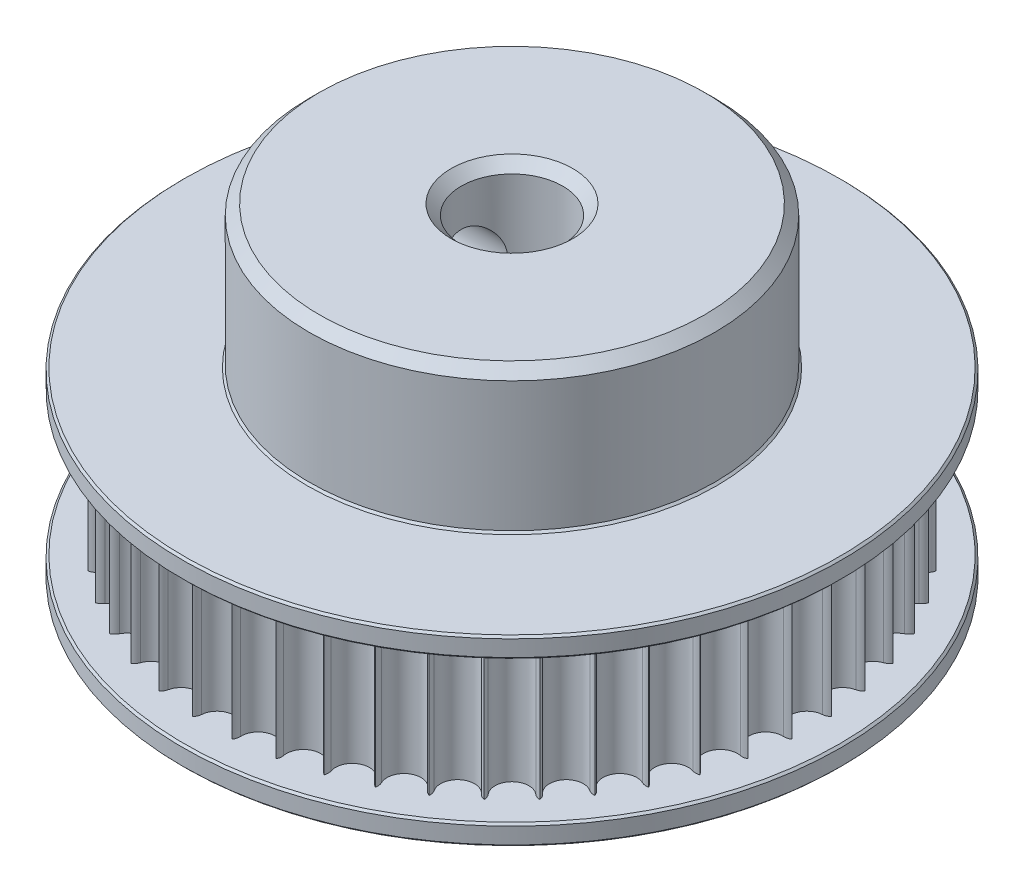
SolidWorks part; units mm, degrees
ref_plane "Front plan" through (0, 0, 0) normal (0, 0, 1) x (1, 0, 0)
ref_plane "Top plan" through (0, 0, 0) normal (0, 1, 0) x (1, 0, 0)
ref_plane "Right plan" through (0, 0, 0) normal (1, 0, 0) x (0, 0, -1)
sketch "Skica2" plane through (0, 0, 0) normal (0, 0, 1) x (1, 0, 0)
  line L0 (10, 8.5) -> (2.5, 8.5)
  line L1 (2.5, 8.5) -> (2.5, -8.5)
  line L2 (2.5, -8.5) -> (3.5, -8.5)
  line L3 (0, -8.5) -> (0, 8.5) construction
  line L4 (0, 8.5) -> (2.5, 8.5)
  line L5 (0, -8.5) -> (2.5, -8.5)
  line L6 (3.5, -8.5) -> (3.5, -7.5)
  line L7 (16.25, 0.5) -> (15, 0.5)
  line L8 (15, 0.5) -> (15, -6.5)
  line L9 (16.25, 0.5) -> (16.25, 1.5)
  line L12 (16.25, -7.5) -> (3.5, -7.5)
  line L13 (16.25, 1.5) -> (10, 1.5)
  line L14 (16.25, -7.5) -> (16.25, -6.5)
  line L15 (15, -6.5) -> (16.25, -6.5)
  line L16 (10, 1.5) -> (10, 8.5)
  point P2 (6.9432, -7.5)
  point P6 (9.875, -7.5)
  point P7 (0, 0)
  point P17 (7.5179, -7.5)
  dimension "D2" = 1
  dimension "D6" = 32.5
  dimension "D3" = 30
  dimension "D1" = 5
  dimension "D8" = 17
  dimension "D4" = 1
  dimension "D7" = 20
  dimension "D9" = 7
  dimension "D5" = 1
revolve "Revolute" add sketch "Skica2" angle 360 about L3 region at (8.0389, -0.5371, 0)
sketch "Sketch2" plane through (0, 0.5, 0) normal (0, -1, 0) x (1, 0, 0)
  line L0 (0, 0) -> (0, 14.5385) construction
  line L1 (0, 0) -> (5.0579, 14.1215) construction
  line L3 (0, 0) -> (-2.1506, 14.845) construction
  circle A1 centre (0, 0) radius 13.7025 construction
  circle A2 centre (0, 0) radius 14.5 construction
  arc A3 (-0.8336, 14.476) -> (0.8336, 14.476) centre (0, 14.5385) ccw
  arc A7 (-1.3782, 14.9366) -> (-2.1506, 14.845) centre (0, 0) ccw
  arc A8 (0, 16.4495) -> (2.1506, 14.845) centre (0.5839, 14.9886) cw
  circle A9 centre (0, 0) radius 15 construction
  arc A10 (1.3782, 14.9366) -> (2.1506, 14.845) centre (0, 0) cw
  arc A11 (1.3782, 14.9366) -> (0.8336, 14.476) centre (1.3322, 14.4387) ccw
  arc A12 (0, 16.4495) -> (-2.1506, 14.845) centre (-0.5839, 14.9886) ccw
  arc A13 (-1.3782, 14.9366) -> (-0.8336, 14.476) centre (-1.3322, 14.4387) cw
  point P0 (0.8326, 11.926)
  dimension "D2" = 1
  dimension "D4" = 0.836
  dimension "D6" = 30
  dimension "D3" = 1.5733
extrude "Cut-Extrude3" cut sketch "Sketch2" along normal up to surface (7 mm away) up to face at (16.25, -6.5, 0)
pattern_circular "CirPattern1" count 48 over 360 about axis through (0, -8.5, 0) along (0, -1, 0) of "Cut-Extrude3"
sketch "Sketch3" plane through (0, 0, 0) normal (1, 0, 0) x (0, 0, -1)
  line L0 (0, 8.5) -> (0, 0.5) construction
  line L1 (2.5, 8.5) -> (-2.5, 8.5) construction
  circle A0 centre (0, 4.5) radius 1.65
  dimension "D1" = 3.3
extrude "Cut-Extrude2" cut sketch "Sketch3" against normal up to next
chamfer "Chamfer1" distance 1 angle 45 1 edges at (3.5, -7.5, 0)
chamfer "Chamfer2" distance 0.5 angle 45 2 edges at (10, 8.5, 0) (2.5, 8.5, 0)
chamfer "Chamfer3" distance 0.1 angle 45 5 edges at (16.25, -7.5, 0) (16.25, -6.5, 0) (16.25, 0.5, 0) (16.25, 1.5, 0) (10, 1.5, 0)
equation "\"`\"=2"
equation "\"D6@Sketch2\"= \"D3@Skica2\""
